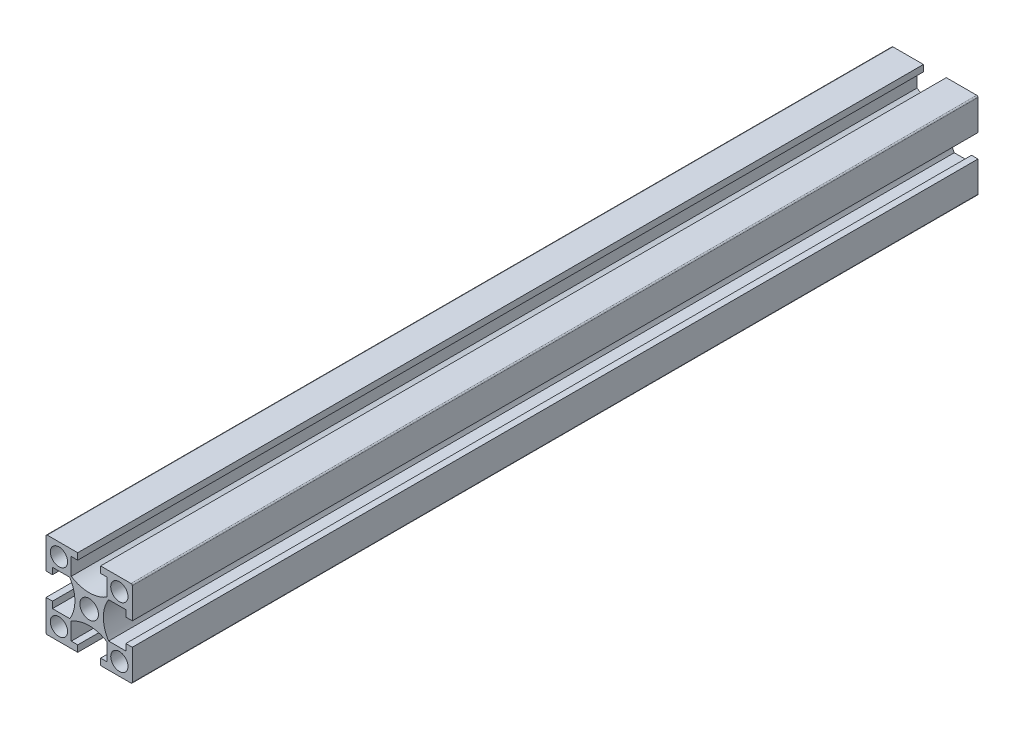
SolidWorks part; units mm, degrees
ref_plane "정면" through (0, 0, 0) normal (0, 0, 1) x (1, 0, 0)
ref_plane "윗면" through (0, 0, 0) normal (0, 1, 0) x (1, 0, 0)
ref_plane "우측면" through (0, 0, 0) normal (1, 0, 0) x (0, 0, -1)
sketch "스케치1" plane through (0, 0, 0) normal (0, 0, 1) x (1, 0, 0)
  line L0 (0, 32.0265) -> (0, -31.6588) construction
  line L1 (-10, 10) -> (-10, -10)
  line L2 (-10, 10) -> (10, 10)
  line L3 (-10, 2.65) -> (-8.5, 2.65)
  line L4 (13.6618, 0) -> (-11.6993, 0) construction
  line L5 (-8.5, 2.65) -> (-8.5, 4.15)
  line L6 (-8.5, 4.15) -> (-4.5032, 4.15)
  line L7 (-10, -2.65) -> (-8.5, -2.65)
  line L8 (-8.5, -2.65) -> (-8.5, -4.15)
  line L9 (-8.5, -4.15) -> (-4.5032, -4.15)
  line L10 (-10, -10) -> (10, -10)
  line L11 (10, 10) -> (10, -10)
  circle A0 centre (-7, 7) radius 2
  circle A1 centre (-7, -7) radius 2
  arc A2 (-4.5032, 4.15) -> (-4.5032, -4.15) centre (-11.0587, 0) cw
  circle A3 centre (0, 0) radius 2.15
  circle A4 centre (7, 7) radius 2
  circle A5 centre (7, -7) radius 2
  point P21 (-10, 0)
  point P23 (-3.3, 0)
  point P31 (0, -10)
  point P32 (0, 10)
  dimension "D3" = 4
  dimension "D9" = 6.7
  dimension "D10" = 4.3
  dimension "D11" = 7.7587
  dimension "D1" = 20
  dimension "D2" = 20
  dimension "D4" = 14
  dimension "D5" = 14
  dimension "D6" = 5.3
  dimension "D7" = 8.3
  dimension "D8" = 1.5
extrude "보스-돌출1" add sketch "스케치1" along normal blind 196 contours A0 | A4 | A3 | A5 | A1 | A2 L6 L5 L3 L1 L7 L8 L9 | L2 L11 L10 L1 region at (-6.6069, 0, 0) region at (-7, 7, 0) region at (-7, -7, 0) region at (0, 0, 0) region at (7, 7, 0) region at (7, -7, 0)
extrude "컷-돌출1" cut sketch "스케치1<3>" along normal up to next contours A2 L6 L5 L3 L1 L7 L8 L9 region at (-6.6069, 0, 0)
sketch "스케치1<3>" plane through (0, 0, 0) normal (0, 0, 1) x (1, 0, 0) same geometry as "스케치1"
pattern_circular "원형 패턴1" count 4 over 360 about axis through (0, 0, 196) along (0, 0, -1) of "컷-돌출1" reverse direction yes
fillet "필렛1" radius 0.3 4 edges at (10, -10, 98) (-10, -10, 98) (-10, 10, 98) (10, 10, 98)
